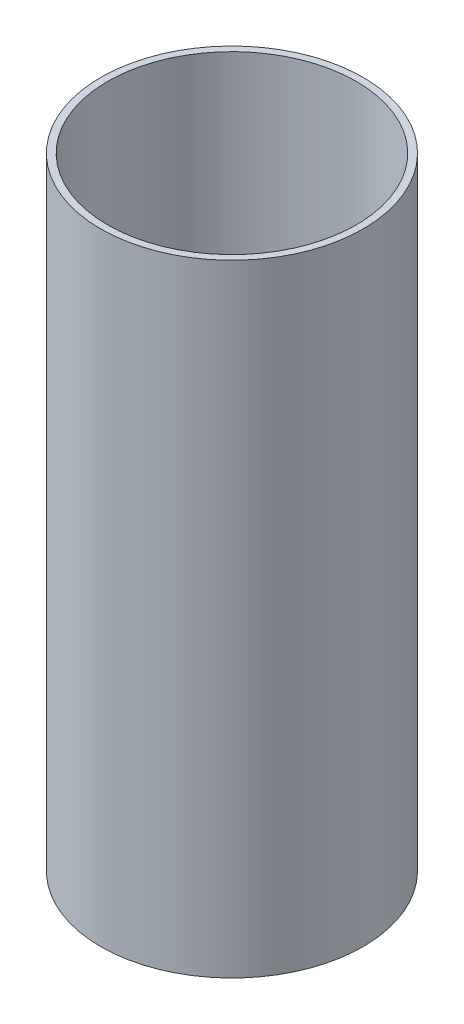
SolidWorks part; units mm, degrees
ref_plane "Front Plane" through (0, 0, 0) normal (0, 0, 1) x (1, 0, 0)
ref_plane "Top Plane" through (0, 0, 0) normal (0, 1, 0) x (1, 0, 0)
ref_plane "Right Plane" through (0, 0, 0) normal (1, 0, 0) x (0, 0, -1)
sketch "Sketch1" plane through (0, 0, 0) normal (0, 1, 0) x (1, 0, 0)
  line L0 (-5.5563, 0) -> (-13.0562, 0) construction
  circle A0 centre (0, 0) radius 5.5563 construction
  circle A1 centre (0, 0) radius 19
  circle A3 centre (-13.0562, 0) radius 2.5
  circle A4 centre (0, 0) radius 18
  circle A5 centre (0, 0) radius 8
  dimension "D1" = 11.1125
  dimension "D2" = 38
  dimension "D4" = 5
  dimension "D5" = 36
  dimension "D6" = 16
  dimension "D3" = 7.5
extrude "Boss-Extrude1" add sketch "Sketch1" along normal blind 3 contours A4 A0 A3 | A1 A4 region at (-18.4626, 0, 0) region at (-17.4909, 0, 0)
extrude "Boss-Extrude2" add sketch "Sketch1<5>" along normal blind 90 contours A1 A4 region at (-18.4626, 0, 0)
sketch "Sketch1<5>" plane through (0, 0, 0) normal (0, 1, 0) x (1, 0, 0) same geometry as "Sketch1"
sketch "Sketch2" plane through (0, 0, 0) normal (1, 0, 0) x (0, 0, -1)
  line L0 (0, 45) -> (0, 17) construction
  line L2 (19, 45) -> (-19, 45) construction
  line L3 (19, 0) -> (19, 90) construction
  line L4 (-19, 90) -> (-19, 0) construction
  circle A0 centre (0, 17) radius 4.7625 construction
  circle A1 centre (0, 17) radius 5.25
  dimension "D2" = 9.525
  dimension "D3" = 10.5
  dimension "D1" = 28
extrude "Cut-Extrude1" cut sketch "Sketch2" against normal through all
